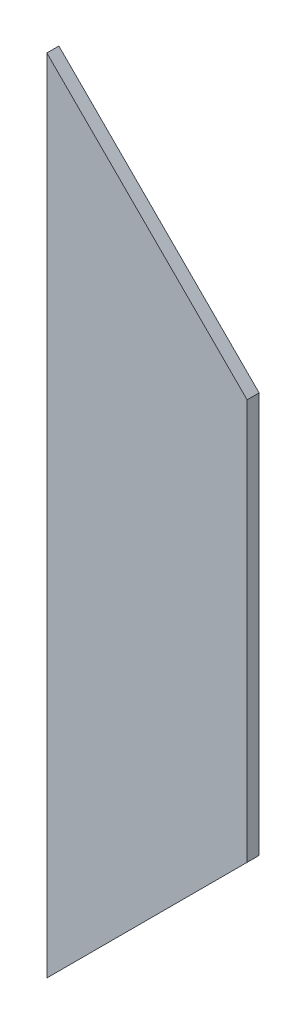
SolidWorks part; units mm, degrees
material "Сосна"
ref_plane "Спереди" through (0, 0, 0) normal (0, 0, 1) x (1, 0, 0)
ref_plane "Сверху" through (0, 0, 0) normal (0, 1, 0) x (1, 0, 0)
ref_plane "Справа" through (0, 0, 0) normal (1, 0, 0) x (0, 0, -1)
sketch "Эскиз1" plane through (0, 0, 0) normal (0, 0, 1) x (1, 0, 0)
  line L0 (0, 0) -> (0, 200)
  line L1 (0, 0) -> (50, 50)
  line L2 (50, 50) -> (50, 150)
  line L3 (50, 150) -> (0, 200)
  dimension "D1" = 200
  dimension "D2" = 50
  dimension "D3" = 45
  dimension "D4" = 45
extrude "Бобышка-Вытянуть1" add sketch "Эскиз1" along normal blind 3
sketch "Эскиз3" plane through (0, 0, 0) normal (-1, 0, 0) x (0, 0, 1)
  line L0 (1.5, 200) -> (1.5, -113.6649) construction
  line L1 (3, 200) -> (0, 200) construction
sketch "Эскиз4" plane through (50, 0, 0) normal (1, 0, 0) x (0, 0, -1)
  line L0 (-1.5, 150) -> (-1.5, -28.0184) construction
  line L1 (-3, 150) -> (0, 150) construction
